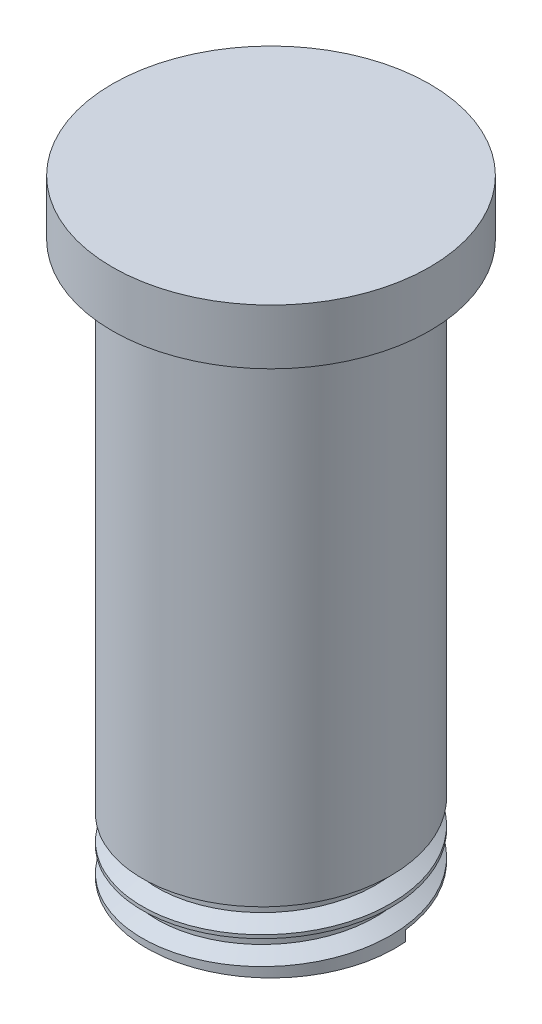
SolidWorks part; units mm, degrees
ref_plane "Front Plane" through (0, 0, 0) normal (0, 0, 1) x (1, 0, 0)
ref_plane "Top Plane" through (0, 0, 0) normal (0, 1, 0) x (1, 0, 0)
ref_plane "Right Plane" through (0, 0, 0) normal (1, 0, 0) x (0, 0, -1)
sketch "Sketch2" plane through (0, 0, 0) normal (0, 1, 0) x (1, 0, 0)
  circle A0 centre (0, 0) radius 11.5
extrude "Boss-Extrude1" add sketch "Sketch2" along normal blind 4
sketch "Sketch3" plane through (0, 0, 0) normal (0, -1, 0) x (-1, 0, 0)
  circle A0 centre (0, 0) radius 9
extrude "Boss-Extrude2" add sketch "Sketch3" along normal blind 40
thread "Thread1" pitch 2 method cut profile "Thread Profile2" start angle 5, offset 1, length 5, pitch 2, diameter 18
ref_plane "Plane2" through (8.9658, -41, -0.7844) normal (0.0872, 0, 0.9962) x (0.9962, 0, -0.0872)
sketch "Thread Profile2" plane through (8.9658, -41, -0.7844) normal (0.0872, 0, 0.9962) x (0.9962, 0, -0.0872)
  line L0 (0, 0) -> (0, 2) construction
  line L11 (0, 0) -> (0, 1.75)
  line L12 (0, 1.75) -> (-1.0825, 1.125)
  line L13 (-1.0825, 1.125) -> (-1.0825, 0.625)
  line L15 (-1.0825, 0.625) -> (0, 0)
  line L17 (-1.0825, 0.875) -> (0, 0.875) construction
  point P2 (0, 0)
  dimension "Pitch" = 2
  dimension "Profile_Angle" = 60
  dimension "Profile_Land" = 0.5
  dimension "Profile_Height" = 1.0825
